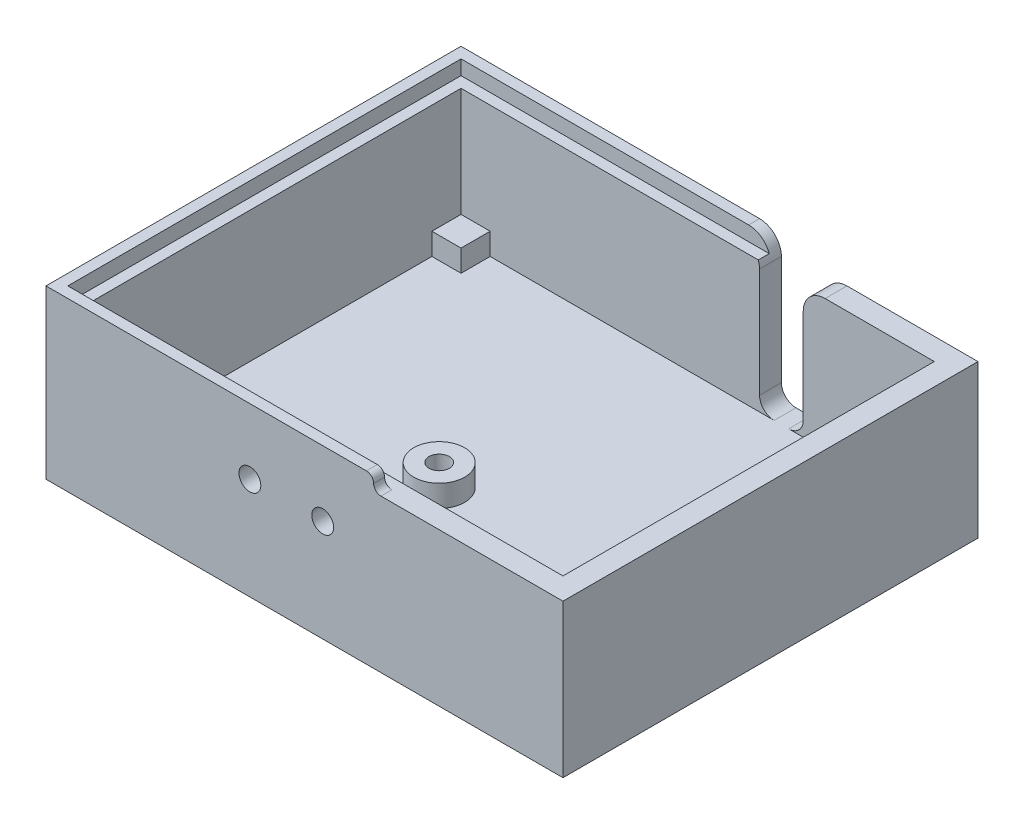
SolidWorks part; units mm, degrees
ref_plane "Plano frontal" through (0, 0, 0) normal (0, 0, 1) x (1, 0, 0)
ref_plane "Plano superior" through (0, 0, 0) normal (0, 1, 0) x (1, 0, 0)
ref_plane "Plano direito" through (0, 0, 0) normal (1, 0, 0) x (0, 0, -1)
sketch "Sketch1" plane through (0, 0, 0) normal (0, 1, 0) x (1, 0, 0)
  line L0 (32.5, 25.5) -> (-32.5, -25.5) construction
  line L1 (-32.5, 25.5) -> (32.5, 25.5) construction
  line L2 (-32.5, 25.5) -> (-32.5, -25.5) construction
  line L3 (-32.5, -25.5) -> (32.5, -25.5) construction
  line L4 (32.5, 25.5) -> (32.5, -25.5) construction
  line L5 (-35.5, 28.5) -> (35.5, 28.5)
  line L6 (35.5, 28.5) -> (35.5, -28.5)
  line L7 (-35.5, -28.5) -> (35.5, -28.5)
  line L8 (-35.5, 28.5) -> (-35.5, -28.5)
  dimension "D1" = 65
  dimension "D2" = 51
  dimension "D3" = 3
extrude "Boss-Extrude1" add sketch "Sketch1" along normal blind 3
sketch "Sketch2" plane through (0, 3, 0) normal (0, 1, 0) x (1, 0, 0)
  line L0 (-32.5, 25.5) -> (-32.5, -25.5)
  line L1 (-32.5, -25.5) -> (32.5, -25.5)
  line L2 (32.5, -25.5) -> (32.5, 25.5)
  line L3 (32.5, 25.5) -> (-32.5, 25.5)
  line L4 (-35.5, 28.5) -> (-35.5, -28.5)
  line L5 (-35.5, -28.5) -> (35.5, -28.5)
  line L6 (35.5, -28.5) -> (35.5, 28.5)
  line L7 (35.5, 28.5) -> (-35.5, 28.5)
  line L8 (-35.5, 28.5) -> (-35.5, -28.5)
  line L9 (-35.5, -28.5) -> (35.5, -28.5)
  line L10 (35.5, -28.5) -> (35.5, 28.5)
  line L11 (35.5, 28.5) -> (-35.5, 28.5)
  dimension "D1" = 0
  dimension "D2" = 3
extrude "Boss-Extrude2" add sketch "Sketch2" along normal blind 18
sketch "Sketch3" plane through (0, 3, 0) normal (0, 1, 0) x (1, 0, 0)
  line L0 (32.5, 0) -> (0, 0) construction
  line L1 (-32.5, 25.5) -> (-28.5, 25.5)
  line L2 (-32.5, 25.5) -> (-32.5, 21.5)
  line L3 (-32.5, 21.5) -> (-28.5, 21.5)
  line L4 (-28.5, 25.5) -> (-28.5, 21.5)
  line L5 (32.5, -25.5) -> (32.5, 25.5) construction
  line L6 (0, 0) -> (0, 25.5) construction
  line L7 (32.5, 25.5) -> (-32.5, 25.5) construction
  line L8 (28.5, 25.5) -> (28.5, 21.5)
  line L9 (32.5, 21.5) -> (28.5, 21.5)
  line L10 (32.5, 25.5) -> (32.5, 21.5)
  line L11 (32.5, 25.5) -> (28.5, 25.5)
  line L12 (32.5, -25.5) -> (28.5, -25.5)
  line L13 (32.5, -25.5) -> (32.5, -21.5)
  line L14 (32.5, -21.5) -> (28.5, -21.5)
  line L15 (28.5, -25.5) -> (28.5, -21.5)
  line L16 (-28.5, -25.5) -> (-28.5, -21.5)
  line L17 (-32.5, -21.5) -> (-28.5, -21.5)
  line L18 (-32.5, -25.5) -> (-32.5, -21.5)
  line L19 (-32.5, -25.5) -> (-28.5, -25.5)
  dimension "D1" = 4
  dimension "D2" = 4
extrude "Boss-Extrude3" add sketch "Sketch3" along normal blind 3
sketch "Sketch4" plane through (0, 3, 0) normal (0, 1, 0) x (1, 0, 0)
  line L0 (-32.5, 25.5) -> (-32.5, -25.5) construction
  line L1 (-28.5, -25.5) -> (28.5, -25.5) construction
  circle A0 centre (-4.5, -5.5) radius 3.5
  dimension "D1" = 7
  dimension "D3" = 28
  dimension "D4" = 20
extrude "Boss-Extrude4" add sketch "Sketch4" along normal blind 3
sketch "Sketch5" plane through (0, 6, 0) normal (0, 1, 0) x (1, 0, 0)
  circle A0 centre (-4.5, -5.5) radius 1.4
  dimension "D1" = 2.8
extrude "Cut-Extrude1" cut sketch "Sketch5" against normal up to next
sketch "Sketch6" plane through (0, 21, 0) normal (0, 1, 0) x (1, 0, 0)
  line L0 (34, 27) -> (-34, 27)
  line L1 (-34, 27) -> (-34, -27)
  line L2 (-34, -27) -> (34, -27)
  line L3 (34, -27) -> (34, 27)
  line L4 (35.5, 28.5) -> (-35.5, 28.5)
  line L5 (-35.5, 28.5) -> (-35.5, -28.5)
  line L6 (-35.5, -28.5) -> (35.5, -28.5)
  line L7 (35.5, -28.5) -> (35.5, 28.5)
  line L8 (35.5, 28.5) -> (-35.5, 28.5)
  line L9 (-35.5, 28.5) -> (-35.5, -28.5)
  line L10 (-35.5, -28.5) -> (35.5, -28.5)
  line L11 (35.5, -28.5) -> (35.5, 28.5)
  dimension "D1" = 0
  dimension "D2" = 1.5
extrude "Boss-Extrude5" add sketch "Sketch6" along normal blind 2
sketch "Sketch7" plane through (0, 0, 28.5) normal (0, 0, 1) x (1, 0, 0)
  line L0 (35.5, 23) -> (35.5, 0) construction
  line L1 (35.5, 21) -> (9.5, 21)
  line L2 (35.5, 21) -> (35.5, 23)
  line L3 (35.5, 23) -> (9.5, 23)
  line L4 (9.5, 21) -> (9.5, 23)
  dimension "D1" = 2
  dimension "D2" = 26
extrude "Cut-Extrude2" cut sketch "Sketch7" against normal through all
fillet "Fillet1" radius 1 4 edges at (9.5, 23, -27.75) (9.5, 21, -27.75) (9.5, 23, 27.75) (9.5, 21, 27.75)
sketch "Sketch8" plane through (0, 0, -28.5) normal (0, 0, -1) x (-1, 0, 0)
  line L1 (-14.5, 23.872) -> (-8.5, 23.872)
  line L2 (-14.5, 23.872) -> (-14.5, 5)
  line L3 (-12.5, 3) -> (-10.5, 3)
  line L4 (-8.5, 23.872) -> (-8.5, 5)
  line L6 (-35.5, 21) -> (-35.5, 0) construction
  line L7 (-35.5, 0) -> (35.5, 0) construction
  arc A0 (-10.5, 3) -> (-8.5, 5) centre (-10.5, 5) ccw
  arc A1 (-12.5, 3) -> (-14.5, 5) centre (-12.5, 5) cw
  dimension "D4" = 2
  dimension "D1" = 27
  dimension "D2" = 21
  dimension "D3" = 3
extrude "Cut-Extrude3" cut sketch "Sketch8" against normal up to next
fillet "Fillet2" radius 3 1 edges at (14.5, 21, -27)
fillet "Fillet3" radius 3 1 edges at (8.5, 23, -27.75)
sketch "Sketch9" plane through (0, 0, 28.5) normal (0, 0, 1) x (1, 0, 0)
  line L0 (-35.5, 14) -> (35.5, 14) construction
  line L1 (-35.5, 23) -> (-35.5, 0) construction
  line L2 (35.5, 21) -> (35.5, 0) construction
  line L3 (-35.5, 0) -> (35.5, 0) construction
  circle A0 centre (2.5, 14) radius 1.5
  circle A1 centre (-7.5, 14) radius 1.5
  dimension "D1" = 14
  dimension "D4" = 3
  dimension "D5" = 3
  dimension "D2" = 33
  dimension "D3" = 10
extrude "Cut-Extrude4" cut sketch "Sketch9" against normal up to next
